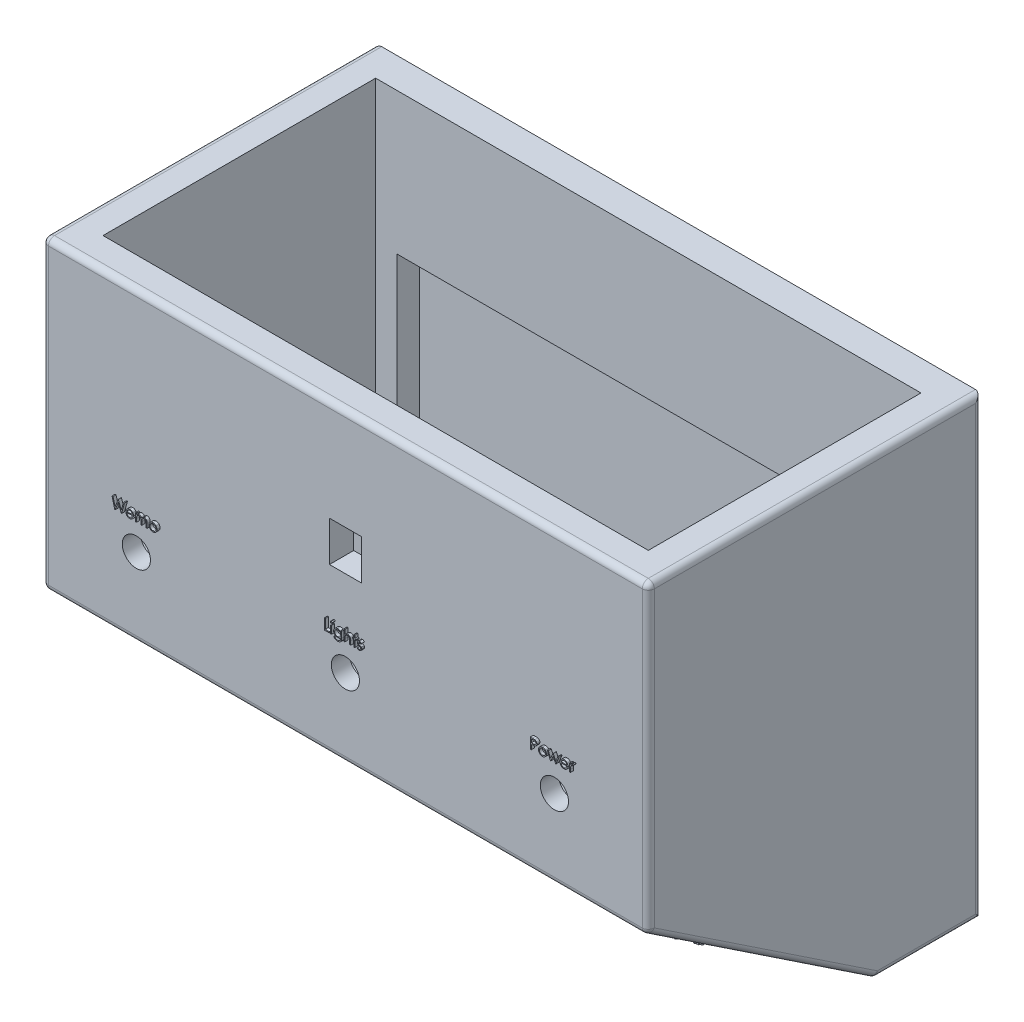
SolidWorks part; units mm, degrees
ref_plane "Front Plane" through (0, 0, 0) normal (0, 0, 1) x (1, 0, 0)
ref_plane "Top Plane" through (0, 0, 0) normal (0, 1, 0) x (1, 0, 0)
ref_plane "Right Plane" through (0, 0, 0) normal (1, 0, 0) x (0, 0, -1)
sketch "Sketch2" plane through (0, 0, 0) normal (0, 0, 1) x (1, 0, 0)
  line L1 (-100, 75) -> (100, 75)
  line L2 (-100, 75) -> (-100, -75)
  line L3 (-100, -75) -> (100, -75)
  line L4 (100, 75) -> (100, -75)
  line L5 (-100, 75) -> (100, -75) construction
  line L6 (-100, -75) -> (100, 75) construction
  point P0 (0, 0)
  dimension "D1" = 150
  dimension "D2" = 200
extrude "Boss-Extrude1" add sketch "Sketch2" along normal blind 35
sketch "Sketch3" plane through (0, 0, 35) normal (0, 0, 1) x (1, 0, 0)
  line L0 (100, -75) -> (100, 75) construction
  line L1 (-100, 75) -> (100, 75)
  line L2 (-100, 75) -> (-100, -25)
  line L3 (-100, -25) -> (100, -25)
  line L4 (100, 75) -> (100, -25)
  dimension "D1" = 100
extrude "Boss-Extrude2" add sketch "Sketch3" along normal blind 75
loft "Loft3" add section face at (0, -50, 35) section face at (0, -25, 72.5) connector at (-100, -75, 35) connector at (-100, -25, 110)
sketch "Sketch6" plane through (0, -68.0769, 45.3846) normal (0, -0.8321, 0.5547) x (1, 0, 0)
  line L1 (-33, 22.408) -> (13, 22.408)
  line L2 (-33, 22.408) -> (-33, 42.908)
  line L3 (-33, 42.908) -> (13, 42.908)
  line L4 (13, 22.408) -> (13, 42.908)
  line L5 (-33, 22.408) -> (13, 42.908) construction
  line L6 (-33, 42.908) -> (13, 22.408) construction
  line L7 (36, 18.658) -> (64, 18.658)
  line L8 (36, 18.658) -> (36, 46.658)
  line L9 (36, 46.658) -> (64, 46.658)
  line L10 (64, 18.658) -> (64, 46.658)
  line L11 (36, 18.658) -> (64, 46.658) construction
  line L12 (36, 46.658) -> (64, 18.658) construction
  line L13 (-100, 77.658) -> (100, 77.658) construction
  line L14 (-81.5, 9.7438) -> (-58.5, 9.7438)
  line L15 (-100, -12.4808) -> (-100, 77.658) construction
  line L16 (-81.5, 9.7438) -> (-81.5, 55.5722)
  line L17 (-81.5, 55.5722) -> (-58.5, 55.5722)
  line L18 (-58.5, 9.7438) -> (-58.5, 55.5722)
  line L19 (-81.5, 9.7438) -> (-58.5, 55.5722) construction
  line L20 (-81.5, 55.5722) -> (-58.5, 9.7438) construction
  line L21 (89.1768, 18.158) -> (73.7768, 18.158)
  line L22 (89.1768, 18.158) -> (89.1768, 46.658)
  line L23 (89.1768, 46.658) -> (73.7768, 46.658)
  line L24 (73.7768, 18.158) -> (73.7768, 46.658)
  line L25 (89.1768, 18.158) -> (73.7768, 46.658) construction
  line L26 (89.1768, 46.658) -> (73.7768, 18.158) construction
  line L27 (73.7768, 38.408) -> (89.1768, 38.408)
  line L28 (73.7768, 38.408) -> (73.7768, 26.408)
  line L29 (73.7768, 26.408) -> (89.1768, 26.408)
  line L30 (89.1768, 38.408) -> (89.1768, 26.408)
  line L31 (73.7768, 38.408) -> (89.1768, 26.408) construction
  line L32 (73.7768, 26.408) -> (89.1768, 38.408) construction
  line L33 (-31.75, 41.408) -> (11.75, 41.408)
  line L34 (-31.75, 41.408) -> (-31.75, 23.908)
  line L35 (-31.75, 23.908) -> (11.75, 23.908)
  line L36 (11.75, 41.408) -> (11.75, 23.908)
  line L37 (-31.75, 41.408) -> (11.75, 23.908) construction
  line L38 (-31.75, 23.908) -> (11.75, 41.408) construction
  line L39 (36, 39.066) -> (64, 39.066)
  line L40 (36, 39.066) -> (36, 18.658)
  line L41 (36, 18.658) -> (64, 18.658)
  line L42 (64, 39.066) -> (64, 18.658)
  line L43 (-15.5, 42.908) -> (-4.5, 42.908)
  line L44 (-15.5, 42.908) -> (-15.5, 41.408)
  line L45 (-15.5, 41.408) -> (-4.5, 41.408)
  line L46 (-4.5, 42.908) -> (-4.5, 41.408)
  circle A0 centre (-70, 32.658) radius 18.5
  circle A1 centre (-70, 32.658) radius 11.25
  point P2 (-10, 32.658)
  point P7 (50, 32.658)
  point P21 (81.4768, 32.408)
  point P22 (81.4768, 32.408)
  point P31 (-10, 32.658)
  dimension "D1" = 37
  dimension "D12" = 22.5
  dimension "D2" = 20.5
  dimension "D3" = 46
  dimension "D4" = 45
  dimension "D5" = 45
  dimension "D6" = 45
  dimension "D7" = 30
  dimension "D8" = 60
  dimension "D9" = 60
  dimension "D10" = 28
  dimension "D11" = 28
  dimension "D13" = 23
  dimension "D14" = 28.5
  dimension "D15" = 15.4
  dimension "D16" = 12
  dimension "D17" = 43.5
  dimension "D18" = 17.5
  dimension "D19" = 11
  dimension "D20" = 16.25
sketch "Sketch8" plane through (0, -68.0769, 45.3846) normal (0, -0.8321, 0.5547) x (1, 0, 0)
  line L1 (-100, 77.658) -> (100, 77.658)
  line L2 (-100, 77.658) -> (-100, -12.4808)
  line L3 (-100, -12.4808) -> (100, -12.4808)
  line L4 (100, 77.658) -> (100, -12.4808)
sketch "Sketch9" plane through (0, 75, 0) normal (0, 1, 0) x (1, 0, 0)
  line L1 (-100, 0) -> (100, 0)
  line L2 (-100, 0) -> (-100, -110)
  line L3 (-100, -110) -> (100, -110)
  line L4 (100, 0) -> (100, -110)
shell "Shell2" thickness 10 removed face at (0, 75, 55)
sketch "Sketch26" plane through (0, -75, 0) normal (0, -1, 0) x (1, 0, 0)
  line L0 (0, 0) -> (0, 35) construction
  line L1 (-100, 35) -> (100, 35) construction
  line L3 (14.25, 2) -> (-14.25, 2)
  line L4 (14.25, 2) -> (14.25, 33)
  line L5 (14.25, 33) -> (-14.25, 33)
  line L6 (-14.25, 2) -> (-14.25, 33)
  line L7 (14.25, 2) -> (-14.25, 33) construction
  line L8 (14.25, 33) -> (-14.25, 2) construction
  point P5 (0, 17.5)
  dimension "D1" = 31
  dimension "D2" = 28.5
extrude "Cut-Extrude12" cut sketch "Sketch26" against normal blind 15
sketch "Sketch28" plane through (0, -75, 0) normal (0, -1, 0) x (1, 0, 0)
  line L0 (14.25, 2) -> (14.25, 33) construction
  line L1 (14.25, 33) -> (-14.25, 33) construction
  ellipse E0 centre (14.25, 17.25) end of major axis (6.15, 17.25) minor radius 7
  ellipse E1 centre (-14.25, 17.25) end of major axis (-22.35, 17.25) minor radius 7
  dimension "D1" = 7
  dimension "D2" = 8.75
  dimension "D3" = 8.1
  dimension "D4" = 2
extrude "Cut-Extrude13" cut sketch "Sketch28" against normal blind 9
sketch "Sketch29" plane through (0, -60, 0) normal (0, -1, 0) x (1, 0, 0)
  line L0 (-14.25, 10) -> (14.25, 10) construction
  circle A0 centre (0, 10) radius 5
  dimension "D1" = 10
extrude "Cut-Extrude14" cut sketch "Sketch29" against normal blind 7.5
fillet "Fillet1" radius 2 2 edges at (0, -52.5, 10) (0, -60, 5)
fillet "Fillet2" radius 2 12 edges at (100, -75, 17.5) (100, -50, 72.5) (100, 75, 55) (100, 0, 0) (-100, 0, 0) (-100, 75, 55) (-100, -50, 72.5) (-100, -75, 17.5) (0, 75, 110) (100, 25, 110) (0, -25, 110) (-100, 25, 110)
fillet "Fillet3" radius 2 3 edges at (-99.4142, -74.4142, 34.8226) (99.4142, -74.4142, 34.8226) (0, -75, 35)
sketch "Sketch30" plane through (0, -66, 0) normal (0, -1, 0) x (1, 0, 0)
  line L0 (14.25, 17.25) -> (22.35, 17.25) construction
  line L1 (14.25, 24.25) -> (14.25, 10.25) construction
  line L2 (14.25, 10.25) -> (14.25, 24.25) construction
  line L7 (22.35, 17.25) -> (-22.35, 17.25) construction
  line L8 (0, 17.25) -> (0, 25.5372) construction
  line L9 (-19.35, 17.25) -> (-19.35, 20.6868) construction
  circle A0 centre (19.35, 17.25) radius 1.05
  circle A1 centre (-19.35, 17.25) radius 1.05
  ellipse E0 centre (14.25, 17.25) end of major axis (6.15, 17.25) minor radius 7 (14.25, 10.25) -> (14.25, 24.25) ccw construction
  ellipse E1 centre (14.25, 17.25) end of major axis (6.15, 17.25) minor radius 7 (14.25, 10.25) -> (14.25, 24.25) ccw construction
  ellipse E2 centre (-14.25, 17.25) end of major axis (-22.35, 17.25) minor radius 7 (-14.25, 24.25) -> (-14.25, 10.25) ccw construction
  dimension "D1" = 2.1
  dimension "D2" = 3
  dimension "D3" = 3
  dimension "D4" = 2
extrude "Cut-Extrude16" cut sketch "Sketch30" against normal blind 10
sketch "Sketch34" plane through (0, 0, 110) normal (0, 0, 1) x (1, 0, 0)
  line L0 (0, 0) -> (-98, 0) construction
  line L1 (-98, 73) -> (-98, -23.9296) construction
  line L2 (0, 0) -> (0, 73) construction
  line L3 (98, 73) -> (-98, 73) construction
  circle A0 centre (-69, 0) radius 4.65
  circle A1 centre (-69, 0) radius 3.5
  circle A2 centre (0, 0) radius 4.65
  circle A3 centre (0, 0) radius 3.5
  circle A4 centre (69, 0) radius 4.65
  circle A5 centre (69, 0) radius 3.5
  dimension "D1" = 9.3
  dimension "D2" = 7
  dimension "D3" = 29
  dimension "D4" = 3
extrude "Cut-Extrude18" cut sketch "Sketch34" against normal blind 15 contours A3 | A5 | A1
extrude "Cut-Extrude19" cut sketch "Sketch34<3>" against normal blind 6
sketch "Sketch34<3>" plane through (0, 0, 110) normal (0, 0, 1) x (1, 0, 0) same geometry as "Sketch34"
fillet "Fillet4" radius 2 3 edges at (-65.5, 0, 104) (3.5, 0, 104) (72.5, 0, 104)
sketch "Sketch35" plane through (0, 0, 10) normal (0, 0, 1) x (1, 0, 0)
  line L1 (83, -28.25) -> (-83, -28.25)
  line L2 (83, -28.25) -> (83, 28.25)
  line L3 (83, 28.25) -> (-83, 28.25)
  line L4 (-83, -28.25) -> (-83, 28.25)
  line L5 (83, -28.25) -> (-83, 28.25) construction
  line L6 (83, 28.25) -> (-83, -28.25) construction
  point P0 (0, 0)
  dimension "D1" = 56.5
  dimension "D2" = 166
extrude "Cut-Extrude20" cut sketch "Sketch35" against normal blind 7.5
sketch "Sketch38" plane through (0, -68.0769, 45.3846) normal (0, -0.8321, 0.5547) x (1, 0, 0)
  text T0 "           Volume/\r\nChange Playlist" font "Century Gothic" height 3.5
extrude "Boss-Extrude8" add sketch "Sketch38" along normal blind 1
sketch "Sketch39" plane through (0, 0, 110) normal (0, 0, 1) x (1, 0, 0)
  line L0 (0, 0) -> (0, 9.7465) construction
  line L1 (0, 9.7465) -> (75.4341, 9.7465) construction
  line L2 (75.4341, 9.7465) -> (-74.7186, 9.7465) construction
sketch "Sketch42" plane through (0, 0, 2.5) normal (0, 0, 1) x (1, 0, 0)
  line L0 (69.0994, 0) -> (69.0994, 9.7465) construction
  line L1 (-69.0387, 0) -> (-69.0387, 17.9151) construction
  line L2 (0, 9.7465) -> (75.4341, 9.7465) construction
  text T0 "Power"
  text T1 "Lights"
  text T2 "Wemo"
  point P2 (0, 0)
  point P5 (0, 0)
  point P6 (69.0994, 9.7465)
extrude "Boss-Extrude10" add sketch "Sketch42" along normal blind 1 from surface starting at face at (-64.35, 0, 110)
extrude "Cut-Extrude23" cut sketch "Sketch6" against normal blind 15 contours L36 L33 L34 L35 | L18 A0 | L16 A0 | L8 L39 L10 L9 | L29 L24 L21 L22 | L24 L27 L22 L23 region at (-10, -49.9615, 72.5577) region at (50, -44.3013, 81.048) region at (-84.351, -49.9615, 72.5577) region at (-55.649, -49.9615, 72.5577) region at (81.4768, -55.7165, 63.9252) region at (81.4768, -44.4838, 80.7742)
ref_plane "Plane7" through (-31.75, -54.8151, 65.2773) normal (1, 0, 0) x (0, 0, -1)
extrude "Cut-Extrude25" cut sketch "Sketch6<6>" against normal blind 8 contours L1 L4 L3 L2 L33 L36 L35 L34 region at (-32.4964, -49.9615, 72.5577)
sketch "Sketch6<6>" plane through (0, -68.0769, 45.3846) normal (0, -0.8321, 0.5547) x (1, 0, 0) same geometry as "Sketch6"
extrude "Cut-Extrude26" cut sketch "Sketch6<7>" against normal blind 5 contours L18 A0 L16 A1 region at (-81.4564, -49.9615, 72.5577)
sketch "Sketch6<7>" plane through (0, -68.0769, 45.3846) normal (0, -0.8321, 0.5547) x (1, 0, 0) same geometry as "Sketch6"
extrude "Cut-Extrude27" cut sketch "Sketch6<8>" against normal blind 7 contours L39 L8 L7 L10 region at (50, -52.0671, 69.3993)
sketch "Sketch6<8>" plane through (0, -68.0769, 45.3846) normal (0, -0.8321, 0.5547) x (1, 0, 0) same geometry as "Sketch6"
extrude "Cut-Extrude28" cut sketch "Sketch6<9>" against normal blind 7 contours L24 L29 L22 L27 region at (81.4768, -50.1002, 72.3497)
sketch "Sketch6<9>" plane through (0, -68.0769, 45.3846) normal (0, -0.8321, 0.5547) x (1, 0, 0) same geometry as "Sketch6"
extrude "Cut-Extrude29" cut sketch "Sketch6<10>" against normal blind 15 contours L46 L3 L44 L33 region at (-10, -44.6919, 80.4622)
sketch "Sketch6<10>" plane through (0, -68.0769, 45.3846) normal (0, -0.8321, 0.5547) x (1, 0, 0) same geometry as "Sketch6"
sketch "Sketch46" plane through (0, 0, 110) normal (0, 0, 1) x (1, 0, 0)
  line L0 (0, -25.5937) -> (0, 55.0917) construction
  line L1 (98, -25.5937) -> (-98, -25.5937) construction
  line L2 (0, 55.0917) -> (-98, 55.0917) construction
  line L3 (-98, 73) -> (-98, -23.9296) construction
  line L5 (-5.25, 41.584) -> (5.25, 41.584)
  line L6 (-5.25, 41.584) -> (-5.25, 28.334)
  line L7 (-5.25, 28.334) -> (5.25, 28.334)
  line L8 (5.25, 41.584) -> (5.25, 28.334)
  line L9 (-5.25, 41.584) -> (5.25, 28.334) construction
  line L10 (-5.25, 28.334) -> (5.25, 41.584) construction
  line L11 (-5.25, 37.834) -> (5.25, 37.834)
  line L12 (-5.25, 37.834) -> (-5.25, 41.584)
  line L13 (-5.25, 41.584) -> (5.25, 41.584)
  line L14 (5.25, 37.834) -> (5.25, 41.584)
  point P5 (0, 34.959)
  dimension "D1" = 10.5
  dimension "D2" = 13.25
  dimension "D3" = 3.75
extrude "Cut-Extrude31" cut sketch "Sketch46" against normal blind 8 contours L11 L6 L7 L8 region at (0, 33.084, 110)
extrude "Cut-Extrude32" cut sketch "Sketch46<5>" against normal blind 15 contours L6 L11 L8 L5 region at (0, 39.709, 110)
sketch "Sketch46<5>" plane through (0, 0, 110) normal (0, 0, 1) x (1, 0, 0) same geometry as "Sketch46"
sketch "Sketch5" plane through (0, -72.7941, 121.3235) normal (0, -0.5145, 0.8575) x (1, 0, 0)
  line L1 (-250, 55.737) -> (250, 55.737)
  line L2 (-250, 55.737) -> (-250, -90.0368)
  line L3 (-250, -90.0368) -> (250, -90.0368)
  line L4 (250, 55.737) -> (250, -90.0368)
  line L5 (136, -14.25) -> (164, -14.25)
  line L6 (136, -14.25) -> (136, 14.25)
  line L7 (136, 14.25) -> (164, 14.25)
  line L8 (164, -14.25) -> (164, 14.25)
  line L9 (136, -14.25) -> (164, 14.25) construction
  line L10 (136, 14.25) -> (164, -14.25) construction
  line L11 (23, -10.5) -> (-23, -10.5)
  line L12 (23, -10.5) -> (23, 10.5)
  line L13 (23, 10.5) -> (-23, 10.5)
  line L14 (-23, -10.5) -> (-23, 10.5)
  line L15 (23, -10.5) -> (-23, 10.5) construction
  line L16 (23, 10.5) -> (-23, -10.5) construction
  circle A0 centre (-150, 0) radius 18.5
  point P8 (150, 0)
  point P9 (-250, -17.1499)
  point P16 (0, 0)
  dimension "D1" = 37
  dimension "D2" = 100
  dimension "D4" = 28
  dimension "D5" = 28.5
  dimension "D6" = 100
  dimension "D7" = 21
  dimension "D8" = 46
